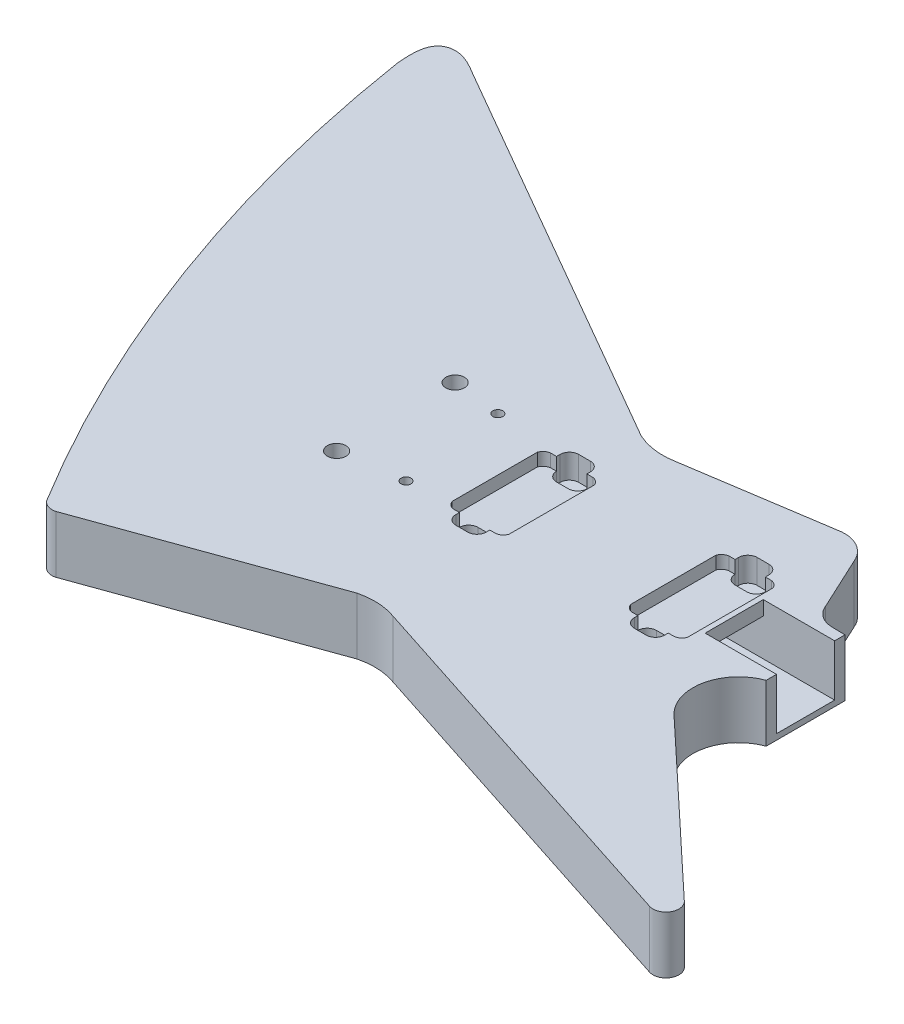
SolidWorks part; units mm, degrees
ref_plane "Front Plane" through (0, 0, 0) normal (0, 0, 1) x (1, 0, 0)
ref_plane "Top Plane" through (0, 0, 0) normal (0, 1, 0) x (1, 0, 0)
ref_plane "Right Plane" through (0, 0, 0) normal (1, 0, 0) x (0, 0, -1)
ref_plane "Plane1" through (0, 20, 0) normal (0, 1, 0) x (1, 0, 0)
sketch "Sketch1" plane through (0, 20, 0) normal (0, 1, 0) x (1, 0, 0)
  line L0 (563.9649, 507.5137) -> (563.9649, 562.7364)
  line L1 (563.9649, 562.7364) -> (554.6908, 562.8948)
  line L2 (539.8539, 573.2061) -> (522.5243, 610.43)
  line L3 (497.9312, 623.6342) -> (399.8309, 608.6087)
  line L4 (371.9236, 612.0224) -> (95.3107, 771.4941)
  line L5 (212.6322, 361.1733) -> (367.6546, 417.0844)
  line L6 (394.091, 415.822) -> (660.2315, 329.5749)
  line L7 (669.267, 344.8773) -> (553.7312, 453.2399)
  arc A0 (554.6908, 562.8948) -> (539.8539, 573.2061) centre (554.9679, 579.1236) cw
  arc A1 (522.5243, 610.43) -> (497.9312, 623.6342) centre (502.4406, 602.5283) ccw
  arc A2 (399.8309, 608.6087) -> (371.9236, 612.0224) centre (391.2113, 653.9219) cw
  arc A3 (60.287, 752.9025) -> (202.7629, 364.7399) centre (1107.1005, 916.9084) ccw
  arc A4 (202.7629, 364.7399) -> (212.6322, 361.1733) centre (210.2265, 369.9546) ccw
  arc A5 (367.6546, 417.0844) -> (394.091, 415.822) centre (378.7977, 372.9989) cw
  arc A6 (660.2315, 329.5749) -> (669.267, 344.8773) centre (663.0383, 338.2363) ccw
  arc A7 (553.7312, 453.2399) -> (563.9649, 507.5137) centre (574.8412, 477.3612) cw
  spline S0 degree 3 poles (60.287, 752.9025) (59.4087, 762.7695) (58.561, 776.2044) (76.9429, 783.2985) (86.7531, 776.4937) (95.3107, 771.4941) knots 0 0 0 0 0.5 0.5 1 1 1 1
extrude "Boss-Extrude1" add sketch "Sketch1" against normal blind 40
sketch "Sketch2" plane through (0, 20, 0) normal (0, 1, 0) x (-1, 0, 0)
  line L0 (-375.961, -499.3953) -> (-375.961, -501.8953)
  line L1 (-375.961, -501.8953) -> (-380.1974, -501.8953)
  line L2 (-385.2646, -506.0868) -> (-385.2646, -565.7325)
  line L3 (-380.1974, -569.9241) -> (-375.961, -569.9241)
  line L4 (-375.961, -569.9241) -> (-375.961, -572.4241)
  line L5 (-369.461, -578.9241) -> (-361.1958, -578.9241)
  line L6 (-354.6958, -572.4241) -> (-354.6958, -569.9241)
  line L7 (-354.6958, -569.9241) -> (-350.4594, -569.9241)
  line L8 (-345.3922, -565.7325) -> (-345.3922, -506.0868)
  line L9 (-350.4594, -501.8953) -> (-354.6958, -501.8953)
  line L10 (-354.6958, -501.8953) -> (-354.6958, -499.3953)
  line L11 (-361.1958, -492.8953) -> (-369.461, -492.8953)
  arc A0 (-380.1974, -501.8953) -> (-385.2646, -506.0868) centre (-379.3951, -508.0239) ccw
  arc A1 (-385.2646, -565.7325) -> (-380.1974, -569.9241) centre (-379.3951, -563.7954) ccw
  arc A2 (-375.961, -572.4241) -> (-369.461, -578.9241) centre (-369.461, -572.4241) ccw
  arc A3 (-361.1958, -578.9241) -> (-354.6958, -572.4241) centre (-361.1958, -572.4241) ccw
  arc A4 (-350.4594, -569.9241) -> (-345.3922, -565.7325) centre (-351.2617, -563.7954) ccw
  arc A5 (-345.3922, -506.0868) -> (-350.4594, -501.8953) centre (-351.2617, -508.0239) ccw
  arc A6 (-354.6958, -499.3953) -> (-361.1958, -492.8953) centre (-361.1958, -499.3953) ccw
  arc A7 (-369.461, -492.8953) -> (-375.961, -499.3953) centre (-369.461, -499.3953) ccw
extrude "Cut-Extrude1" cut sketch "Sketch2" against normal blind 9
sketch "Sketch3" plane through (0, 11, 0) normal (0, 1, 0) x (-1, 0, 0)
  line L0 (-361.1958, -492.8953) -> (-369.461, -492.8953)
  line L1 (-375.961, -499.3953) -> (-375.961, -501.8953)
  line L2 (-369.461, -508.3953) -> (-361.191, -508.3953)
  line L3 (-354.6958, -501.8953) -> (-354.6958, -499.3953)
  arc A0 (-354.6958, -499.3953) -> (-361.1958, -492.8953) centre (-361.1958, -499.3953) ccw
  arc A1 (-369.461, -492.8953) -> (-375.961, -499.3953) centre (-369.461, -499.3953) ccw
  arc A2 (-375.961, -501.8953) -> (-369.461, -508.3953) centre (-369.461, -501.8953) ccw
  arc A3 (-361.191, -508.3953) -> (-354.6958, -501.8953) centre (-361.191, -501.9) ccw
extrude "Cut-Extrude2" cut sketch "Sketch3" against normal blind 8
sketch "Sketch4" plane through (0, 20, 0) normal (0, 1, 0) x (-1, 0, 0)
  line L0 (-479.7441, -572.4241) -> (-479.7441, -569.9241)
  line L1 (-479.7441, -569.9241) -> (-475.5077, -569.9241)
  line L2 (-470.4406, -565.7325) -> (-470.4406, -506.0868)
  line L3 (-475.5077, -501.8953) -> (-479.7441, -501.8953)
  line L4 (-479.7441, -501.8953) -> (-479.7441, -499.3953)
  line L5 (-486.2441, -492.8953) -> (-494.5094, -492.8953)
  line L6 (-501.0094, -499.3953) -> (-501.0094, -501.8953)
  line L7 (-501.0094, -501.8953) -> (-505.2458, -501.8953)
  line L8 (-510.313, -506.0868) -> (-510.313, -565.7325)
  line L9 (-505.2458, -569.9241) -> (-501.0094, -569.9241)
  line L10 (-501.0094, -569.9241) -> (-501.0094, -572.4241)
  line L11 (-494.5094, -578.9241) -> (-486.2441, -578.9241)
  arc A0 (-475.5077, -569.9241) -> (-470.4406, -565.7325) centre (-476.3101, -563.7954) ccw
  arc A1 (-470.4406, -506.0868) -> (-475.5077, -501.8953) centre (-476.3101, -508.0239) ccw
  arc A2 (-479.7441, -499.3953) -> (-486.2441, -492.8953) centre (-486.2441, -499.3953) ccw
  arc A3 (-494.5094, -492.8953) -> (-501.0094, -499.3953) centre (-494.5094, -499.3953) ccw
  arc A4 (-505.2458, -501.8953) -> (-510.313, -506.0868) centre (-504.4434, -508.0239) ccw
  arc A5 (-510.313, -565.7325) -> (-505.2458, -569.9241) centre (-504.4434, -563.7954) ccw
  arc A6 (-501.0094, -572.4241) -> (-494.5094, -578.9241) centre (-494.5094, -572.4241) ccw
  arc A7 (-486.2441, -578.9241) -> (-479.7441, -572.4241) centre (-486.2441, -572.4241) ccw
extrude "Cut-Extrude3" cut sketch "Sketch4" against normal blind 9
sketch "Sketch5" plane through (0, 11, 0) normal (0, 1, 0) x (-1, 0, 0)
  line L0 (-486.2441, -492.8953) -> (-494.5094, -492.8953)
  line L1 (-501.0094, -499.3953) -> (-501.0094, -501.8953)
  line L2 (-494.5141, -508.3953) -> (-486.2441, -508.3953)
  line L3 (-479.7441, -501.8953) -> (-479.7441, -499.3953)
  arc A0 (-494.5094, -492.8953) -> (-501.0094, -499.3953) centre (-494.5094, -499.3953) ccw
  arc A1 (-501.0094, -501.8953) -> (-494.5141, -508.3953) centre (-494.5141, -501.9) ccw
  arc A2 (-486.2441, -508.3953) -> (-479.7441, -501.8953) centre (-486.2441, -501.8953) ccw
  arc A3 (-479.7441, -499.3953) -> (-486.2441, -492.8953) centre (-486.2441, -499.3953) ccw
extrude "Cut-Extrude4" cut sketch "Sketch5" against normal blind 8
sketch "Sketch6" plane through (0, 11, 0) normal (0, 1, 0) x (-1, 0, 0)
  line L0 (-369.461, -578.9241) -> (-361.1958, -578.9241)
  line L1 (-354.6958, -572.4241) -> (-354.6958, -569.9241)
  line L2 (-361.1911, -563.4241) -> (-369.4611, -563.4241)
  line L3 (-375.961, -569.9241) -> (-375.961, -572.4241)
  arc A0 (-361.1958, -578.9241) -> (-354.6958, -572.4241) centre (-361.1958, -572.4241) ccw
  arc A1 (-354.6958, -569.9241) -> (-361.1911, -563.4241) centre (-361.1911, -569.9194) ccw
  arc A2 (-369.4611, -563.4241) -> (-375.961, -569.9241) centre (-369.4611, -569.9241) ccw
  arc A3 (-375.961, -572.4241) -> (-369.461, -578.9241) centre (-369.461, -572.4241) ccw
extrude "Cut-Extrude5" cut sketch "Sketch6" against normal blind 8
sketch "Sketch7" plane through (0, 11, 0) normal (0, 1, 0) x (-1, 0, 0)
  line L0 (-494.5094, -578.9241) -> (-486.2441, -578.9241)
  line L1 (-479.7441, -572.4241) -> (-479.7441, -569.9241)
  line L2 (-486.2441, -563.4241) -> (-494.5141, -563.4241)
  line L3 (-501.0094, -569.9241) -> (-501.0094, -572.4241)
  arc A0 (-486.2441, -578.9241) -> (-479.7441, -572.4241) centre (-486.2441, -572.4241) ccw
  arc A1 (-479.7441, -569.9241) -> (-486.2441, -563.4241) centre (-486.2441, -569.9241) ccw
  arc A2 (-494.5141, -563.4241) -> (-501.0094, -569.9241) centre (-494.5141, -569.9193) ccw
  arc A3 (-501.0094, -572.4241) -> (-494.5094, -578.9241) centre (-494.5094, -572.4241) ccw
extrude "Cut-Extrude6" cut sketch "Sketch7" against normal blind 8
ref_plane "Plane2" through (0, 0, -514.7664) normal (0, 0, 1) x (1, 0, 0)
sketch "Sketch8" plane through (0, 0, -514.7664) normal (0, 0, 1) x (1, 0, 0)
  line L0 (463.9649, -16) -> (563.9649, -16)
  line L1 (563.9649, -16) -> (563.9649, 20)
  line L2 (563.9649, 20) -> (513.9649, 20)
  line L3 (513.9649, 20) -> (513.9649, 10)
  line L4 (513.9649, 10) -> (463.9649, 10)
  line L5 (463.9649, 10) -> (463.9649, -16)
extrude "Cut-Extrude7" cut sketch "Sketch8" against normal blind 40.73
hole_wizard "Ø7.0 (7) Diameter Hole1" positions "Sketch10" profile "Sketch9" hole size "Ø7.0" standard "ANSI Metric"
sketch "Sketch10" plane through (0, 20, 0) normal (0, 1, 0) x (1, 0, 0)
  point P0 (308.1791, 575.3111)
  point P1 (316.8769, 502.2974)
sketch "Sketch9" plane through (308.1791, 20, -575.3111) normal (1, 0, 0) x (0, 0, 1)
  line L0 (0, 0) -> (0, 29)
  line L1 (0, 29) -> (3.5, 29)
  line L2 (3.5, 29) -> (3.5, 0)
  line L5 (3.5, 0) -> (0, 0)
  line L10 (0, 29) -> (-3.5, 29) construction
  line L11 (0, -6.35) -> (0, 107.95) construction
  dimension "Hole Dia." = 7
  dimension "Hole Depth" = 29
  dimension "Drill Angle" = 180
hole_wizard "Ø13.0 (13) Diameter Hole1" positions "Sketch12" profile "Sketch11" hole size "Ø13.0" standard "ANSI Metric"
sketch "Sketch12" plane through (0, 20, 0) normal (0, 1, 0) x (1, 0, 0)
  point P0 (274.3359, 496.2335)
  point P1 (274.3359, 579.2131)
sketch "Sketch11" plane through (274.3359, 20, -496.2335) normal (1, 0, 0) x (0, 0, 1)
  line L0 (0, 0) -> (0, 29)
  line L1 (0, 29) -> (6.5, 29)
  line L2 (6.5, 29) -> (6.5, 0)
  line L5 (6.5, 0) -> (0, 0)
  line L10 (0, 29) -> (-6.5, 29) construction
  line L11 (0, -6.35) -> (0, 107.95) construction
  dimension "Hole Dia." = 13
  dimension "Hole Depth" = 29
  dimension "Drill Angle" = 180
